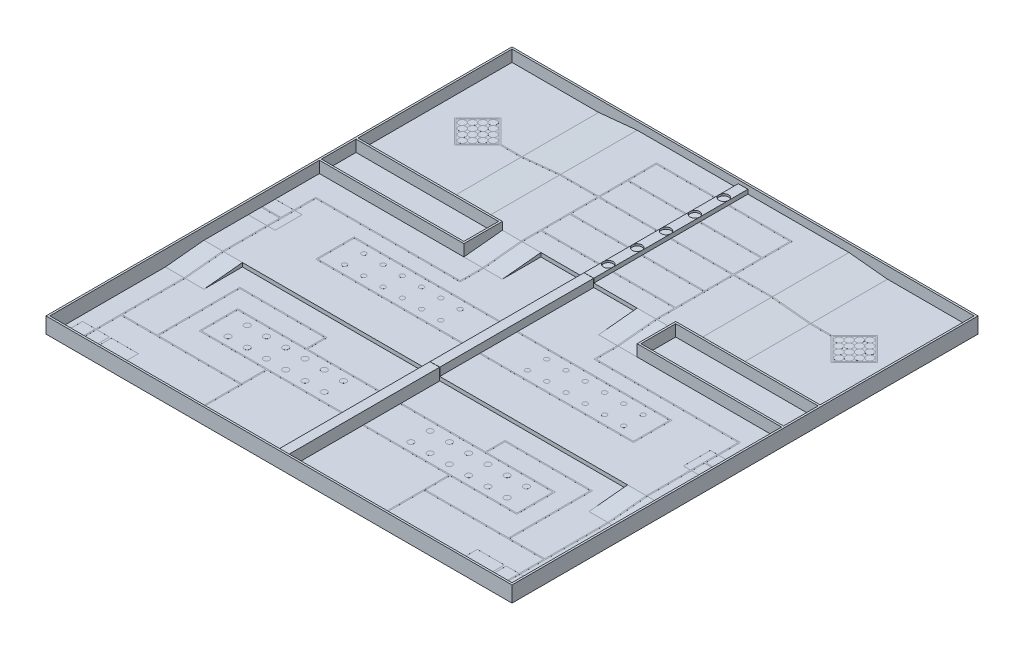
SolidWorks part; units mm, degrees
ref_plane "Front Plane" through (0, 0, 0) normal (0, 0, 1) x (1, 0, 0)
ref_plane "Top Plane" through (0, 0, 0) normal (0, 1, 0) x (1, 0, 0)
ref_plane "Right Plane" through (0, 0, 0) normal (1, 0, 0) x (0, 0, -1)
sketch "Sketch1" plane through (0, 0, 0) normal (0, 1, 0) x (1, 0, 0)
  line L1 (-6050, 6050) -> (6050, 6050)
  line L2 (-6050, 6050) -> (-6050, -6050)
  line L3 (-6050, -6050) -> (6050, -6050)
  line L4 (6050, 6050) -> (6050, -6050)
  line L5 (-6050, 6050) -> (6050, -6050) construction
  line L6 (-6050, -6050) -> (6050, 6050) construction
  point P0 (0, 0)
  dimension "D1" = 12100
  dimension "D2" = 12100
extrude "Boss-Extrude1" add sketch "Sketch1" along normal blind 10
sketch "Sketch2" plane through (0, 10, 0) normal (0, 1, 0) x (1, 0, 0)
  line L0 (0, 6332.5328) -> (0, -6669.5431) construction
  line L1 (-125, 6050) -> (-125, -6050)
  line L2 (125, 6050) -> (125, -6050)
  line L3 (-125, 6050) -> (125, 6050)
  line L4 (6050, 6050) -> (-6050, 6050) construction
  line L5 (-125, -6050) -> (125, -6050)
  line L6 (-125, 6332.5328) -> (-125, -6669.5431) construction
  line L7 (125, 6332.5328) -> (125, -6669.5431) construction
  line L8 (-6050, -6050) -> (6050, -6050) construction
  dimension "D1" = 125
  dimension "D2" = 125
extrude "Boss-Extrude2" add sketch "Sketch2" along normal blind 310
sketch "Sketch3" plane through (0, 10, 0) normal (0, 1, 0) x (1, 0, 0)
  line L0 (-6000, -6000) -> (-6000, 6000)
  line L1 (-6050, -6050) -> (6050, -6050)
  line L2 (-6050, -6050) -> (-6050, 6050)
  line L3 (-6050, 6050) -> (6050, 6050)
  line L4 (6050, -6050) -> (6050, 6050)
  line L5 (-6050, -6050) -> (6050, 6050) construction
  line L6 (-6050, 6050) -> (6050, -6050) construction
  line L7 (-6000, 6000) -> (6000, 6000)
  line L8 (6000, -6000) -> (6000, 6000)
  line L9 (-6000, -6000) -> (6000, -6000)
  point P0 (0, 0)
  dimension "D1" = 50
extrude "Boss-Extrude3" add sketch "Sketch3" along normal blind 400
sketch "Sketch4" plane through (0, 10, 0) normal (0, 1, 0) x (1, 0, 0)
  line L0 (-6863.0858, 0) -> (7124.8929, 0) construction
  line L1 (-6050, -2000) -> (6050, -2000)
  line L2 (-6050, 2000) -> (6050, 2000)
  line L3 (-6050, 2000) -> (-6050, 0)
  line L4 (-6050, 6050) -> (-6050, -6050) construction
  line L5 (-6050, 0) -> (-6050, -2000)
  line L6 (6050, 2000) -> (6050, -2000)
  line L7 (6050, -6050) -> (6050, 6050) construction
  line L9 (-6863.0858, 2000) -> (7124.8929, 2000) construction
  line L10 (-6863.0858, -2000) -> (7124.8929, -2000) construction
  dimension "D1" = 2000
  dimension "D2" = 2000
extrude "Boss-Extrude4" add sketch "Sketch4" along normal blind 100
sketch "Sketch5" plane through (0, 10, 0) normal (0, 1, 0) x (1, 0, 0)
  line L0 (-6000, 6000) -> (-6000, 2000)
  line L1 (-6000, 2000) -> (6000, 2000)
  line L2 (6000, 2000) -> (6000, 6000)
  line L3 (6000, 6000) -> (-6000, 6000)
extrude "Boss-Extrude5" add sketch "Sketch5" along normal blind 200
sketch "Sketch8" plane through (0, 110, 0) normal (0, 1, 0) x (1, 0, 0)
  line L0 (2250, 2000) -> (2250, 1000)
  line L1 (6000, 2000) -> (125, 2000) construction
  line L2 (2250, 1000) -> (6050, 1000)
  line L3 (6050, -6050) -> (6050, 6050) construction
  line L4 (6050, 1000) -> (6050, 2000)
  line L5 (6050, 2000) -> (2250, 2000)
  line L6 (6000, 1950) -> (2300, 1950)
  line L7 (2300, 1950) -> (2300, 1050)
  line L8 (2300, 1050) -> (6000, 1050)
  line L9 (6000, 1050) -> (6000, 1950)
  line L10 (0, 6607.4153) -> (0, -6987.4348) construction
  line L11 (-6050, 1000) -> (-6050, 2000)
  line L12 (-2250, 1000) -> (-6050, 1000)
  line L13 (-2250, 2000) -> (-2250, 1000)
  line L14 (-6050, 2000) -> (-2250, 2000)
  line L15 (-6000, 1050) -> (-6000, 1950)
  line L16 (-2300, 1050) -> (-6000, 1050)
  line L17 (-2300, 1950) -> (-2300, 1050)
  line L18 (-6000, 1950) -> (-2300, 1950)
  dimension "D1" = 1000
  dimension "D2" = 3800
  dimension "D3" = 50
extrude "Boss-Extrude9" add sketch "Sketch8" along normal blind 300
sketch "Sketch9" plane through (0, 210, 0) normal (0, 1, 0) x (1, 0, 0)
  line L0 (6000, 6000) -> (2750, 6000)
  line L1 (6000, 6000) -> (125, 6000) construction
  line L2 (2750, 6000) -> (2750, 2000)
  line L3 (2750, 2000) -> (6000, 2000)
  line L4 (6000, 2000) -> (6000, 6000) construction
  line L5 (6000, 2000) -> (6000, 6000)
  line L6 (0, 7222.203) -> (0, -7135.0065) construction
  line L7 (-2750, 2000) -> (-6000, 2000)
  line L8 (-2750, 6000) -> (-2750, 2000)
  line L9 (-6000, 6000) -> (-2750, 6000)
  line L10 (-6000, 2000) -> (-6000, 6000)
  dimension "D1" = 3250
  dimension "D2" = 4000
extrude "Cut-Extrude2" cut sketch "Sketch9" against normal blind 100
sketch "Sketch10" plane through (0, 0, -6000) normal (0, 0, 1) x (1, 0, 0)
  line L0 (2750, 210) -> (2750, 110)
  line L1 (2750, 110) -> (3750, 110)
  line L2 (6000, 110) -> (2750, 110) construction
  line L3 (3750, 110) -> (2750, 210)
  line L4 (0, 741.9991) -> (0, -415.2884) construction
  line L5 (-2750, 110) -> (-3750, 110)
  line L6 (-2750, 210) -> (-2750, 110)
  line L7 (-3750, 110) -> (-2750, 210)
  dimension "D1" = 1000
extrude "Boss-Extrude10" add sketch "Sketch10" along normal blind 4000
sketch "Sketch11" plane through (2250, 0, 0) normal (-1, 0, 0) x (0, 0, 1)
  line L0 (-2000, 210) -> (-2000, 110)
  line L1 (-2000, 110) -> (-1000, 110)
  line L2 (-1000, 110) -> (-2000, 210)
extrude "Boss-Extrude11" add sketch "Sketch11" along normal blind 1000
sketch "Sketch12" plane through (-2250, 0, 0) normal (1, 0, 0) x (0, 0, -1)
  line L1 (2000, 210) -> (2000, 110)
  line L2 (2000, 110) -> (1000, 110)
  line L3 (1000, 110) -> (2000, 210)
extrude "Boss-Extrude12" add sketch "Sketch12" along normal blind 1000
sketch "Sketch13" plane through (6000, 0, 0) normal (-1, 0, 0) x (0, 0, 1)
  line L0 (2000, 110) -> (2000, 10)
  line L1 (2000, 10) -> (3000, 10)
  line L2 (6000, 10) -> (2000, 10) construction
  line L3 (3000, 10) -> (2000, 110)
  dimension "D1" = 1000
extrude "Boss-Extrude13" add sketch "Sketch13" along normal blind 1000
sketch "Sketch14" plane through (-6000, 0, 0) normal (1, 0, 0) x (0, 0, -1)
  line L0 (-2000, 110) -> (-2000, 10)
  line L1 (-2000, 10) -> (-3000, 10)
  line L2 (-3000, 10) -> (-2000, 110)
  dimension "D1" = 1000
extrude "Boss-Extrude14" add sketch "Sketch14" along normal blind 1000
sketch "Sketch15" plane through (0, 320, 0) normal (0, 1, 0) x (1, 0, 0)
  line L0 (-125, 2000) -> (125, 2000)
  line L1 (125, 2000) -> (125, 1995)
  line L2 (125, -6000) -> (125, 6000) construction
  line L3 (125, 1995) -> (-125, 1995)
  line L4 (-125, 2000) -> (-125, -2000) construction
  line L5 (-125, 1995) -> (-125, 2000)
  line L6 (-125, -2000) -> (125, -2000)
  line L7 (125, -2000) -> (125, -2005)
  line L8 (125, -6000) -> (125, -2000) construction
  line L9 (125, -2005) -> (-125, -2005)
  line L10 (-125, 6000) -> (-125, -6000) construction
  line L11 (-125, -2005) -> (-125, -2000)
  dimension "D1" = 5
  dimension "D2" = 5
extrude "Cut-Extrude3" cut sketch "Sketch15" against normal blind 300
sketch "Sketch16" plane through (0, 10, 0) normal (0, 1, 0) x (1, 0, 0)
  line L0 (0, 6376.018) -> (0, -6397.7606) construction
  line L1 (5850, -6000) -> (5850, -5300)
  line L2 (-6000, -6000) -> (6000, -6000) construction
  line L3 (5850, -5300) -> (5150, -5300)
  line L4 (5150, -5300) -> (5150, -6000)
  line L5 (125, -6000) -> (6000, -6000) construction
  line L6 (5150, -6000) -> (5850, -6000)
  line L7 (5100, -6000) -> (5100, -5300)
  line L8 (5100, -5300) -> (4400, -5300)
  line L9 (4400, -5300) -> (4400, -6000)
  line L10 (4400, -6000) -> (5100, -6000)
  line L11 (6000, -6000) -> (6000, -3000) construction
  line L12 (-4400, -5300) -> (-4400, -6000)
  line L13 (-5100, -5300) -> (-4400, -5300)
  line L14 (-5100, -6000) -> (-5100, -5300)
  line L15 (-4400, -6000) -> (-5100, -6000)
  line L16 (-5150, -5300) -> (-5150, -6000)
  line L17 (-5850, -5300) -> (-5150, -5300)
  line L18 (-5850, -6000) -> (-5850, -5300)
  line L19 (-5150, -6000) -> (-5850, -6000)
  dimension "D1" = 150
  dimension "D2" = 700
  dimension "D3" = 700
  dimension "D4" = 50
  dimension "D5" = 700
  dimension "D6" = 700
extrude "Cut-Extrude4" cut sketch "Sketch16" against normal blind 0.5
sketch "Sketch18" plane through (0, 110, 0) normal (0, 1, 0) x (1, 0, 0)
  line L0 (0, 6289.0476) -> (0, -6452.1171) construction
  line L1 (6000, -150) -> (5300, -150)
  line L2 (6000, -2000) -> (6000, 1000) construction
  line L3 (5300, -150) -> (5300, -850)
  line L4 (5300, -850) -> (6000, -850)
  line L5 (6000, -850) -> (6000, -150)
  line L6 (2250, 1000) -> (6000, 1000) construction
  line L7 (-5300, -850) -> (-6000, -850)
  line L8 (-5300, -150) -> (-5300, -850)
  line L9 (-6000, -150) -> (-5300, -150)
  line L10 (-6000, -850) -> (-6000, -150)
  dimension "D1" = 700
  dimension "D2" = 700
  dimension "D3" = 1150
extrude "Cut-Extrude5" cut sketch "Sketch18" against normal blind 0.5
sketch "Sketch19" plane through (0, 10, 0) normal (0, 1, 0) x (1, 0, 0)
  line L0 (0, 6386.8893) -> (0, -6636.9292) construction
  line L1 (4000, -6000) -> (4000, -5750)
  line L2 (125, -6000) -> (4400, -6000) construction
  line L3 (4000, -5750) -> (750, -5750)
  line L4 (750, -5750) -> (750, -6000)
  line L5 (750, -6000) -> (4000, -6000)
  line L6 (4400, -5300) -> (4400, -6000) construction
  line L7 (750, -5875) -> (4000, -5875) construction
  line L8 (-750, -6000) -> (-4000, -6000)
  line L9 (-750, -5750) -> (-750, -6000)
  line L10 (-4000, -5750) -> (-750, -5750)
  line L11 (-4000, -6000) -> (-4000, -5750)
  circle A0 centre (1000, -5875) radius 45
  circle A1 centre (1250, -5875) radius 45
  circle A2 centre (1500, -5875) radius 45
  circle A3 centre (1750, -5875) radius 45
  circle A4 centre (2000, -5875) radius 45
  circle A5 centre (2250, -5875) radius 45
  circle A6 centre (2500, -5875) radius 45
  circle A7 centre (2750, -5875) radius 45
  circle A8 centre (3000, -5875) radius 45
  circle A9 centre (3250, -5875) radius 45
  circle A10 centre (3500, -5875) radius 45
  circle A11 centre (3750, -5875) radius 45
  circle A12 centre (-3750, -5875) radius 45
  circle A13 centre (-3500, -5875) radius 45
  circle A14 centre (-3250, -5875) radius 45
  circle A15 centre (-3000, -5875) radius 45
  circle A16 centre (-2750, -5875) radius 45
  circle A17 centre (-2500, -5875) radius 45
  circle A18 centre (-2250, -5875) radius 45
  circle A19 centre (-2000, -5875) radius 45
  circle A20 centre (-1750, -5875) radius 45
  circle A21 centre (-1500, -5875) radius 45
  circle A22 centre (-1250, -5875) radius 45
  circle A23 centre (-1000, -5875) radius 45
  dimension "D4" = 90
  dimension "D1" = 400
  dimension "D2" = 3250
  dimension "D3" = 250
  dimension "D5" = 250
  dimension "D7" = 2750
  dimension "D6" = 12
extrude "Boss-Extrude15" add sketch "Sketch19" along normal blind 60
sketch "Sketch20" plane through (0, 10, 0) normal (0, 1, 0) x (1, 0, 0)
  line L0 (0, 6278.1763) -> (0, -6517.3449) construction
  line L1 (125, -6000) -> (125, -2000) construction
  line L2 (125, -6000) -> (750, -6000) construction
  line L3 (125, -6000) -> (125, -2005) construction
  circle A0 centre (1125, -3750) radius 75
  circle A1 centre (1625, -3750) radius 75
  circle A2 centre (2125, -3750) radius 75
  circle A3 centre (2625, -3750) radius 75
  circle A4 centre (3125, -3750) radius 75
  circle A5 centre (3625, -3750) radius 75
  circle A6 centre (1625, -3250) radius 75
  circle A7 centre (2125, -3250) radius 75
  circle A8 centre (2625, -3250) radius 75
  circle A9 centre (3125, -3250) radius 75
  circle A10 centre (3625, -3250) radius 75
  circle A11 centre (1125, -3250) radius 75
  circle A12 centre (-1125, -3250) radius 75
  circle A13 centre (-3625, -3250) radius 75
  circle A14 centre (-3125, -3250) radius 75
  circle A15 centre (-2625, -3250) radius 75
  circle A16 centre (-2125, -3250) radius 75
  circle A17 centre (-1625, -3250) radius 75
  circle A18 centre (-3625, -3750) radius 75
  circle A19 centre (-3125, -3750) radius 75
  circle A20 centre (-2625, -3750) radius 75
  circle A21 centre (-2125, -3750) radius 75
  circle A22 centre (-1625, -3750) radius 75
  circle A23 centre (-1125, -3750) radius 75
  dimension "D1" = 150
  dimension "D2" = 2250
  dimension "D3" = 1000
  dimension "D6" = 500
  dimension "D7" = 2500
  dimension "D8" = 1000
  dimension "D4" = 6
  dimension "D5" = 2
extrude "Boss-Extrude16" add sketch "Sketch20" along normal blind 0.5
sketch "Sketch21" plane through (0, 9.5, 0) normal (0, 1, 0) x (1, 0, 0)
  line L0 (5500, -6000) -> (5500, -3000) construction
  line L1 (5150, -6000) -> (5850, -6000) construction
  line L2 (5000, -3000) -> (6000, -3000) construction
  line L3 (5485, -5300) -> (5485, -5635)
  line L4 (5850, -5300) -> (5150, -5300) construction
  line L5 (5150, -5650) -> (5850, -5650) construction
  line L6 (5150, -5300) -> (5150, -6000) construction
  line L7 (5850, -6000) -> (5850, -5300) construction
  line L8 (5515, -5300) -> (5515, -5635)
  line L9 (5150, -5665) -> (5485, -5665)
  line L10 (5150, -5635) -> (5485, -5635)
  line L12 (5850, -5635) -> (5850, -5665)
  line L13 (5485, -6000) -> (5515, -6000)
  line L14 (5150, -5635) -> (5150, -5665)
  line L15 (5485, -5665) -> (5485, -6000)
  line L16 (5515, -5635) -> (5850, -5635)
  line L17 (5515, -5665) -> (5515, -6000)
  line L18 (5150, -5635) -> (5850, -5635) construction
  line L19 (5515, -5665) -> (5850, -5665)
  line L20 (5485, -5300) -> (5485, -3000)
  line L21 (5150, -5665) -> (5850, -5665) construction
  line L22 (5515, -5300) -> (5515, -3000)
  line L23 (5485, -3000) -> (5515, -3000)
  line L24 (0, 6769.1351) -> (0, -7021.8172) construction
  line L25 (-5150, -5650) -> (-5850, -5650) construction
  line L26 (-5500, -6000) -> (-5500, -3000) construction
  line L27 (-5485, -3000) -> (-5515, -3000)
  line L28 (-5515, -5300) -> (-5515, -3000)
  line L29 (-5485, -5300) -> (-5485, -3000)
  line L30 (-5515, -5665) -> (-5850, -5665)
  line L31 (-5515, -5665) -> (-5515, -6000)
  line L32 (-5515, -5635) -> (-5850, -5635)
  line L33 (-5485, -5665) -> (-5485, -6000)
  line L34 (-5150, -5635) -> (-5150, -5665)
  line L35 (-5485, -6000) -> (-5515, -6000)
  line L36 (-5850, -5635) -> (-5850, -5665)
  line L37 (-5150, -5635) -> (-5485, -5635)
  line L38 (-5150, -5665) -> (-5485, -5665)
  line L39 (-5515, -5300) -> (-5515, -5635)
  line L40 (-5485, -5300) -> (-5485, -5635)
  dimension "D1" = 15
  dimension "D2" = 15
  dimension "D3" = 15
extrude "Boss-Extrude17" add sketch "Sketch21" along normal blind 1
sketch "Sketch22" plane through (0, 10, 0) normal (0, 1, 0) x (1, 0, 0)
  line L0 (5485, -4650) -> (2390, -4650) construction
  line L1 (5485, -5300) -> (5485, -3000) construction
  line L2 (-125, -3970) -> (-125, -4000)
  line L3 (5100, -5300) -> (4400, -5300) construction
  line L4 (4400, -5300) -> (4400, -6000) construction
  line L5 (-4548, -4635) -> (-2390, -4635)
  line L6 (5485, -4635) -> (4578, -4635)
  line L7 (5485, -4665) -> (2390, -4665)
  line L8 (5485, -4635) -> (5485, -4665)
  line L9 (2390, -5750) -> (2390, -4665)
  line L10 (4000, -5750) -> (750, -5750) construction
  line L11 (2360, -5750) -> (2360, -4000)
  line L12 (4000, -5750) -> (750, -5750) construction
  line L13 (2360, -4000) -> (125, -4000)
  line L14 (-2360, -5750) -> (-2390, -5750)
  line L15 (-4095, -3030) -> (-4095, -3970)
  line L17 (125, -6000) -> (125, -2005) construction
  line L18 (125, -3970) -> (4095, -3970)
  line L19 (4125, -3000) -> (4125, -4000)
  line L20 (4125, -3000) -> (2340, -3000)
  line L21 (2340, -3000) -> (2340, -2520)
  line L22 (2340, -2520) -> (4548, -2520)
  line L23 (4548, -2520) -> (4548, -4635)
  line L24 (4578, -4635) -> (4578, -2490)
  line L25 (4578, -2490) -> (2310, -2490)
  line L26 (2310, -2490) -> (2310, -3000)
  line L27 (2310, -3000) -> (125, -3000)
  line L28 (125, -6000) -> (125, -2000) construction
  line L29 (125, -3000) -> (125, -3030)
  line L30 (4125, -4000) -> (2390, -4000)
  line L31 (2390, -4000) -> (2390, -4635)
  line L32 (125, -3030) -> (4095, -3030)
  line L33 (4095, -3030) -> (4095, -3970)
  line L34 (125, -6000) -> (750, -6000) construction
  line L35 (2360, -5750) -> (2390, -5750)
  line L36 (4548, -4635) -> (2390, -4635)
  line L37 (125, -3970) -> (125, -4000)
  line L38 (5485, -4635) -> (2390, -4635) construction
  line L39 (0, 6467.6788) -> (0, -7119.9213) construction
  line L40 (-125, -3030) -> (-4095, -3030)
  line L41 (-2390, -4000) -> (-2390, -4635)
  line L42 (-4125, -4000) -> (-2390, -4000)
  line L43 (-125, -3000) -> (-125, -3030)
  line L44 (-2310, -3000) -> (-125, -3000)
  line L45 (-2310, -2490) -> (-2310, -3000)
  line L46 (-4578, -2490) -> (-2310, -2490)
  line L47 (-4578, -4635) -> (-4578, -2490)
  line L48 (-4548, -2520) -> (-4548, -4635)
  line L49 (-2340, -2520) -> (-4548, -2520)
  line L50 (-2340, -3000) -> (-2340, -2520)
  line L51 (-4125, -3000) -> (-2340, -3000)
  line L52 (-4125, -3000) -> (-4125, -4000)
  line L53 (-125, -3970) -> (-4095, -3970)
  line L54 (-2360, -4000) -> (-125, -4000)
  line L55 (-2360, -5750) -> (-2360, -4000)
  line L56 (-2390, -5750) -> (-2390, -4665)
  line L57 (-5485, -4635) -> (-5485, -4665)
  line L58 (-5485, -4665) -> (-2390, -4665)
  line L59 (-5485, -4635) -> (-4578, -4635)
  dimension "D8" = 4000
  dimension "D1" = 650
  dimension "D2" = 2010
  dimension "D5" = 30
  dimension "D6" = 1750
  dimension "D7" = 1000
  dimension "D9" = 30
  dimension "D10" = 30
  dimension "D11" = 30
  dimension "D12" = 30
  dimension "D13" = 30
  dimension "D14" = 480
  dimension "D15" = 30
  dimension "D16" = 2185
  dimension "D17" = 30
  dimension "D18" = 423
  dimension "D3" = 15
  dimension "D4" = 15
extrude "Boss-Extrude18" add sketch "Sketch22" along normal blind 0.5
ref_plane "Plane1" through (5515, 0, 0) normal (-1, 0, 0) x (0, 0, 1)
sketch "Sketch23" plane through (5515, 0, 0) normal (-1, 0, 0) x (0, 0, 1)
  line L0 (2000, 110) -> (2000, 110.5)
  line L1 (2000, 110.5) -> (3000, 10.5)
  line L2 (3000, 10.5) -> (3000, 10)
  line L3 (3000, 10) -> (2000, 110)
  line L4 (3000, 10) -> (2000, 110) construction
  line L7 (3000, 10.5) -> (3000, 10) construction
  dimension "D1" = 0.5
extrude "Boss-Extrude19" add sketch "Sketch23" along normal blind 30
ref_plane "Plane2" through (-5515, 0, 0) normal (1, 0, 0) x (0, 0, -1)
sketch "Sketch24" plane through (-5515, 0, 0) normal (1, 0, 0) x (0, 0, -1)
  line L1 (-3000, 10) -> (-3000, 10.5)
  line L2 (-3000, 10.5) -> (-2000, 110.5)
  line L3 (-2000, 110.5) -> (-2000, 110)
  line L4 (-2000, 110) -> (-3000, 10)
  line L5 (-2000, 110) -> (-3000, 10) construction
  line L7 (-3000, 10.5) -> (-3000, 10) construction
  dimension "D1" = 0.5
extrude "Boss-Extrude20" add sketch "Sketch24" along normal blind 30
sketch "Sketch25" plane through (0, 110, 0) normal (0, 1, 0) x (1, 0, 0)
  line L0 (5515, -2000) -> (5515, -515)
  line L1 (5515, -515) -> (6000, -515)
  line L2 (6000, -850) -> (6000, -150) construction
  line L3 (6000, -515) -> (6000, -485)
  line L4 (6000, -6000) -> (6000, 1000) construction
  line L5 (6000, -485) -> (5515, -485)
  line L6 (5515, -485) -> (5515, 420)
  line L7 (5515, 420) -> (1765, 420)
  line L8 (1765, 420) -> (1765, 1000)
  line L9 (1250, 1000) -> (2250, 1000) construction
  line L10 (1765, 1000) -> (1735, 1000)
  line L11 (1735, 1000) -> (1735, 390)
  line L12 (1735, 390) -> (5485, 390)
  line L13 (5485, 390) -> (5485, -2000)
  line L14 (5000, -2000) -> (5485, -2000) construction
  line L15 (5485, -2000) -> (5515, -2000)
  line L16 (5300, -850) -> (6000, -850) construction
  line L17 (2250, 1000) -> (2250, 2000) construction
  line L18 (2250, 1000) -> (6000, 1000) construction
  line L19 (0, 6919.2774) -> (0, -6916.6346) construction
  line L20 (-5485, -2000) -> (-5515, -2000)
  line L21 (-5485, 390) -> (-5485, -2000)
  line L22 (-1735, 390) -> (-5485, 390)
  line L23 (-1735, 1000) -> (-1735, 390)
  line L24 (-1765, 1000) -> (-1735, 1000)
  line L25 (-1765, 420) -> (-1765, 1000)
  line L26 (-5515, 420) -> (-1765, 420)
  line L27 (-5515, -485) -> (-5515, 420)
  line L28 (-6000, -485) -> (-5515, -485)
  line L29 (-6000, -515) -> (-6000, -485)
  line L30 (-5515, -515) -> (-6000, -515)
  line L31 (-5515, -2000) -> (-5515, -515)
  dimension "D1" = 30
  dimension "D2" = 30
  dimension "D3" = 30
  dimension "D4" = 335
  dimension "D5" = 30
  dimension "D6" = 30
  dimension "D7" = 485
  dimension "D8" = 580
extrude "Boss-Extrude21" add sketch "Sketch25" along normal blind 0.5
sketch "Sketch26" plane through (0, 110, 0) normal (0, 1, 0) x (1, 0, 0)
  line L0 (125, 27.5) -> (4125, 27.5)
  line L1 (125, -2000) -> (125, 1995) construction
  line L2 (4125, 27.5) -> (4125, -972.5)
  line L3 (4125, -972.5) -> (125, -972.5)
  line L4 (125, -942.5) -> (4095, -942.5)
  line L5 (125, -2000) -> (125, 1995) construction
  line L6 (4095, -942.5) -> (4095, -2.5)
  line L7 (4095, -2.5) -> (125, -2.5)
  line L8 (125, -2.5) -> (125, 27.5)
  line L9 (0, 6616.8381) -> (0, -6826.6708) construction
  line L10 (-125, -2.5) -> (-125, 27.5)
  line L11 (-4095, -2.5) -> (-125, -2.5)
  line L12 (-4095, -942.5) -> (-4095, -2.5)
  line L13 (-125, -942.5) -> (-4095, -942.5)
  line L14 (-4125, -972.5) -> (-125, -972.5)
  line L15 (-4125, 27.5) -> (-4125, -972.5)
  line L16 (-125, 27.5) -> (-4125, 27.5)
  line L17 (-125, -942.5) -> (-125, -972.5)
  line L18 (125, -942.5) -> (125, -972.5)
  circle A0 centre (3625, -222.5) radius 60
  circle A1 centre (3125, -222.5) radius 60
  circle A2 centre (2625, -222.5) radius 60
  circle A3 centre (2125, -222.5) radius 60
  circle A4 centre (1625, -222.5) radius 60
  circle A5 centre (1125, -222.5) radius 60
  circle A6 centre (3125, -722.5) radius 60
  circle A7 centre (2625, -722.5) radius 60
  circle A8 centre (2125, -722.5) radius 60
  circle A9 centre (1625, -722.5) radius 60
  circle A10 centre (1125, -722.5) radius 60
  circle A11 centre (3625, -722.5) radius 60
  circle A12 centre (-3625, -722.5) radius 60
  circle A13 centre (-1125, -722.5) radius 60
  circle A14 centre (-1625, -722.5) radius 60
  circle A15 centre (-2125, -722.5) radius 60
  circle A16 centre (-2625, -722.5) radius 60
  circle A17 centre (-3125, -722.5) radius 60
  circle A18 centre (-1125, -222.5) radius 60
  circle A19 centre (-1625, -222.5) radius 60
  circle A20 centre (-2125, -222.5) radius 60
  circle A21 centre (-2625, -222.5) radius 60
  circle A22 centre (-3125, -222.5) radius 60
  circle A23 centre (-3625, -222.5) radius 60
  dimension "D6" = 120
  dimension "D1" = 30
  dimension "D2" = 30
  dimension "D3" = 30
  dimension "D4" = 1000
  dimension "D5" = 4000
  dimension "D7" = 250
  dimension "D8" = 500
  dimension "D11" = 2500
  dimension "D12" = 500
  dimension "D13" = 500
  dimension "D9" = 6
  dimension "D10" = 2
extrude "Boss-Extrude22" add sketch "Sketch26" along normal blind 0.5
ref_plane "Plane3" through (1765, 0, 0) normal (-1, 0, 0) x (0, 0, 1)
sketch "Sketch27" plane through (1765, 0, 0) normal (-1, 0, 0) x (0, 0, 1)
  line L1 (-2000, 210) -> (-1000, 110)
  line L2 (-1000, 110) -> (-1000, 110.5)
  line L3 (-1000, 110.5) -> (-2000, 210.5)
  line L4 (-2000, 210.5) -> (-2000, 210)
  line L5 (-1000, 110) -> (-2000, 210) construction
  line L7 (-1000, 110.5) -> (-1000, 110) construction
  dimension "D1" = 0.5
extrude "Boss-Extrude23" add sketch "Sketch27" along normal blind 30
ref_plane "Plane4" through (-1765, 0, 0) normal (1, 0, 0) x (0, 0, -1)
sketch "Sketch28" plane through (-1765, 0, 0) normal (1, 0, 0) x (0, 0, -1)
  line L1 (1000, 110) -> (2000, 210)
  line L2 (2000, 210) -> (2000, 210.5)
  line L3 (2000, 210.5) -> (1000, 110.5)
  line L4 (1000, 110.5) -> (1000, 110)
  line L5 (2000, 210) -> (1000, 110) construction
  line L6 (1000, 110.5) -> (1000, 110) construction
  dimension "D1" = 0.5
extrude "Boss-Extrude24" add sketch "Sketch28" along normal blind 30
sketch "Sketch29" plane through (0, 210, 0) normal (0, 1, 0) x (1, 0, 0)
  line L0 (1765, 2000) -> (1765, 3985)
  line L1 (1765, 3985) -> (2750, 3985)
  line L3 (2750, 6000) -> (2750, 2000) construction
  line L4 (2750, 3985) -> (2750, 4015)
  line L5 (2750, 4015) -> (1765, 4015)
  line L6 (1765, 4015) -> (1765, 5515)
  line L7 (1765, 5515) -> (125, 5515)
  line L8 (125, 2000) -> (125, 6000) construction
  line L9 (125, 5515) -> (125, 5485)
  line L10 (125, 5485) -> (1735, 5485)
  line L11 (1735, 5485) -> (1735, 4765)
  line L12 (1735, 4765) -> (125, 4765)
  line L13 (125, 2000) -> (125, 6000) construction
  line L14 (125, 4765) -> (125, 4735)
  line L15 (125, 4735) -> (1735, 4735)
  line L16 (1735, 4735) -> (1735, 4015)
  line L17 (1735, 4015) -> (125, 4015)
  line L18 (125, 4015) -> (125, 3985)
  line L19 (125, 3985) -> (1735, 3985)
  line L20 (1735, 3985) -> (1735, 3265)
  line L21 (1735, 3265) -> (125, 3265)
  line L22 (125, 3265) -> (125, 3235)
  line L23 (125, 3235) -> (1735, 3235)
  line L24 (1735, 3235) -> (1735, 2515)
  line L25 (1735, 2515) -> (125, 2515)
  line L26 (125, 2515) -> (125, 2485)
  line L27 (125, 2485) -> (1735, 2485)
  line L28 (1735, 2485) -> (1735, 2000)
  line L29 (1735, 2000) -> (1765, 2000)
  line L30 (2750, 6000) -> (125, 6000) construction
  line L31 (1765, 2000) -> (2250, 2000) construction
  line L32 (0, 6376.8672) -> (0, -1004.6373) construction
  line L33 (-1735, 2000) -> (-1765, 2000)
  line L34 (-1735, 2485) -> (-1735, 2000)
  line L35 (-125, 2485) -> (-1735, 2485)
  line L36 (-125, 2515) -> (-125, 2485)
  line L37 (-1735, 2515) -> (-125, 2515)
  line L38 (-1735, 3235) -> (-1735, 2515)
  line L39 (-125, 3235) -> (-1735, 3235)
  line L40 (-125, 3265) -> (-125, 3235)
  line L41 (-1735, 3265) -> (-125, 3265)
  line L42 (-1735, 3985) -> (-1735, 3265)
  line L43 (-125, 3985) -> (-1735, 3985)
  line L44 (-125, 4015) -> (-125, 3985)
  line L45 (-1735, 4015) -> (-125, 4015)
  line L46 (-1735, 4735) -> (-1735, 4015)
  line L47 (-125, 4735) -> (-1735, 4735)
  line L48 (-125, 4765) -> (-125, 4735)
  line L49 (-1735, 4765) -> (-125, 4765)
  line L50 (-1735, 5485) -> (-1735, 4765)
  line L51 (-125, 5485) -> (-1735, 5485)
  line L52 (-125, 5515) -> (-125, 5485)
  line L53 (-1765, 5515) -> (-125, 5515)
  line L54 (-1765, 4015) -> (-1765, 5515)
  line L55 (-2750, 4015) -> (-1765, 4015)
  line L56 (-2750, 3985) -> (-2750, 4015)
  line L57 (-1765, 3985) -> (-2750, 3985)
  line L58 (-1765, 2000) -> (-1765, 3985)
  dimension "D1" = 30
  dimension "D2" = 30
  dimension "D3" = 30
  dimension "D4" = 30
  dimension "D5" = 1985
  dimension "D6" = 1985
  dimension "D7" = 30
  dimension "D8" = 485
  dimension "D9" = 30
  dimension "D10" = 30
  dimension "D11" = 720
  dimension "D12" = 30
  dimension "D13" = 30
  dimension "D14" = 720
  dimension "D15" = 720
extrude "Boss-Extrude25" add sketch "Sketch29" along normal blind 0.5
ref_plane "Plane5" through (0, 0, -4015) normal (0, 0, 1) x (1, 0, 0)
sketch "Sketch30" plane through (0, 0, -4015) normal (0, 0, 1) x (1, 0, 0)
  line L1 (2750, 210) -> (3750, 110)
  line L2 (3750, 110) -> (3750, 110.5)
  line L3 (3750, 110.5) -> (2750, 210.5)
  line L4 (2750, 210.5) -> (2750, 210)
  line L5 (-2750, 210) -> (-3750, 110)
  line L6 (-3750, 110) -> (-3750, 110.5)
  line L7 (-3750, 110.5) -> (-2750, 210.5)
  line L8 (-2750, 210.5) -> (-2750, 210)
  line L9 (3750, 110) -> (2750, 210) construction
  line L10 (2750, 210.5) -> (2750, 210) construction
  line L11 (-2750, 210) -> (-3750, 110) construction
  line L12 (-2750, 210.5) -> (-2750, 210) construction
  dimension "D1" = 0.5
  dimension "D2" = 0.5
extrude "Boss-Extrude26" add sketch "Sketch30" along normal blind 30
sketch "Sketch31" plane through (0, 110, 0) normal (0, 1, 0) x (1, 0, 0)
  line L0 (3750, 4000) -> (5893.5836, 4000) construction
  line L1 (3750, 3985) -> (3750, 4015) construction
  line L2 (4890.0408, 4992.3625) -> (4890.0408, 3149.0483) construction
  line L3 (0, 6735.0907) -> (0, -332.6816) construction
  line L4 (4890.0408, 4601.0408) -> (4304, 4015)
  line L9 (4304, 3985) -> (4890.0408, 3398.9592)
  line L10 (4890.0408, 3398.9592) -> (5491.0815, 4000)
  line L11 (5491.0815, 4000) -> (4890.0408, 4601.0408)
  line L12 (-4890.0408, 4992.3625) -> (-4890.0408, 3149.0483) construction
  line L13 (3750, 4015) -> (4304, 4015)
  line L14 (3750, 4015) -> (3750, 3985)
  line L15 (3750, 3985) -> (4304, 3985)
  line L16 (5448.6551, 4000) -> (4890.0408, 4558.6144)
  line L17 (4890.0408, 4558.6144) -> (4331.4264, 4000)
  line L18 (4331.4264, 4000) -> (4890.0408, 3441.3856)
  line L19 (4890.0408, 3441.3856) -> (5448.6551, 4000)
  line L20 (3750, 4015) -> (3750, 6000) construction
  line L21 (4890.0408, 4601.0408) -> (4289, 4000) construction
  line L22 (4289, 4000) -> (4890.0408, 3398.9592) construction
  line L23 (6000, 2000) -> (6000, 6000) construction
  line L24 (-3750, 4000) -> (-5893.5836, 4000) construction
  line L25 (-4890.0408, 3441.3856) -> (-5448.6551, 4000)
  line L26 (-4331.4264, 4000) -> (-4890.0408, 3441.3856)
  line L27 (-4890.0408, 4558.6144) -> (-4331.4264, 4000)
  line L28 (-5448.6551, 4000) -> (-4890.0408, 4558.6144)
  line L29 (-3750, 3985) -> (-4304, 3985)
  line L30 (-3750, 4015) -> (-3750, 3985)
  line L31 (-3750, 4015) -> (-4304, 4015)
  line L32 (-5491.0815, 4000) -> (-4890.0408, 4601.0408)
  line L33 (-4890.0408, 3398.9592) -> (-5491.0815, 4000)
  line L34 (-4304, 3985) -> (-4890.0408, 3398.9592)
  line L35 (-4890.0408, 4601.0408) -> (-4304, 4015)
  point P8 (4890.0408, 4000)
  point P40 (-4890.0408, 4000)
  dimension "D1" = 1140.0408
  dimension "D2" = 508.9185
  dimension "D3" = 850
  dimension "D4" = 30
extrude "Boss-Extrude27" add sketch "Sketch31" along normal blind 0.5
sketch "Sketch32" plane through (0, 110, 0) normal (0, 1, 0) x (1, 0, 0)
  line L0 (0, 6397.7606) -> (0, -549.0007) construction
  line L1 (5169.3479, 4279.3072) -> (4610.7336, 3720.6928) construction
  line L2 (5448.6551, 4000) -> (4890.0408, 4558.6144) construction
  line L3 (4610.7336, 4279.3072) -> (5169.3479, 3720.6928) construction
  line L4 (4890.0408, 4558.6144) -> (4331.4264, 4000) construction
  line L5 (4890.0408, 3441.3856) -> (5448.6551, 4000) construction
  line L6 (4331.4264, 4000) -> (4890.0408, 3441.3856) construction
  line L7 (4677.9087, 4346.4823) -> (5236.5231, 3787.868) construction
  line L8 (5102.1728, 4346.4823) -> (4543.5584, 3787.868) construction
  line L9 (5034.9977, 4413.6575) -> (4476.3833, 3855.0431) construction
  line L10 (4476.3833, 4144.9569) -> (5034.9977, 3586.3425) construction
  line L11 (4745.0839, 4413.6575) -> (5303.6982, 3855.0431) construction
  line L12 (-4745.0839, 4413.6575) -> (-5303.6982, 3855.0431) construction
  line L13 (-4476.3833, 4144.9569) -> (-5034.9977, 3586.3425) construction
  line L14 (-5034.9977, 4413.6575) -> (-4476.3833, 3855.0431) construction
  line L15 (-5102.1728, 4346.4823) -> (-4543.5584, 3787.868) construction
  line L16 (-4677.9087, 4346.4823) -> (-5236.5231, 3787.868) construction
  line L17 (-4610.7336, 4279.3072) -> (-5169.3479, 3720.6928) construction
  line L18 (-5169.3479, 4279.3072) -> (-4610.7336, 3720.6928) construction
  circle A1 centre (4890.0408, 4134.3503) radius 94.5
  circle A2 centre (4755.6905, 4268.7006) radius 94.5
  circle A3 centre (5024.3911, 4000) radius 94.5
  circle A4 centre (5158.7413, 3865.6497) radius 94.5
  circle A5 centre (5024.3911, 3731.2994) radius 94.5
  circle A6 centre (4890.0408, 3865.6497) radius 94.5
  circle A7 centre (4755.6905, 4000) radius 94.5
  circle A8 centre (4621.3402, 4134.3503) radius 94.5
  circle A9 centre (4890.0408, 3596.9491) radius 94.5
  circle A10 centre (4755.6905, 3731.2994) radius 94.5
  circle A11 centre (4621.3402, 3865.6497) radius 94.5
  circle A12 centre (4486.9899, 4000) radius 94.5
  circle A13 centre (5293.0916, 4000) radius 94.5
  circle A14 centre (5158.7413, 4134.3503) radius 94.5
  circle A15 centre (5024.3911, 4268.7006) radius 94.5
  circle A16 centre (4890.0408, 4403.0509) radius 94.5
  circle A17 centre (-4890.0408, 4403.0509) radius 94.5
  circle A18 centre (-5024.3911, 4268.7006) radius 94.5
  circle A19 centre (-5158.7413, 4134.3503) radius 94.5
  circle A20 centre (-5293.0916, 4000) radius 94.5
  circle A21 centre (-4486.9899, 4000) radius 94.5
  circle A22 centre (-4621.3402, 3865.6497) radius 94.5
  circle A23 centre (-4755.6905, 3731.2994) radius 94.5
  circle A24 centre (-4890.0408, 3596.9491) radius 94.5
  circle A25 centre (-4621.3402, 4134.3503) radius 94.5
  circle A26 centre (-4755.6905, 4000) radius 94.5
  circle A27 centre (-4890.0408, 3865.6497) radius 94.5
  circle A28 centre (-5024.3911, 3731.2994) radius 94.5
  circle A29 centre (-5158.7413, 3865.6497) radius 94.5
  circle A30 centre (-5024.3911, 4000) radius 94.5
  circle A31 centre (-4755.6905, 4268.7006) radius 94.5
  circle A32 centre (-4890.0408, 4134.3503) radius 94.5
  dimension "D3" = 189
  dimension "D1" = 95
  dimension "D2" = 95
  dimension "D4" = 95
  dimension "D5" = 190
  dimension "D6" = 190
extrude "Boss-Extrude30" add sketch "Sketch32" along normal blind 0.5
sketch "Sketch33" plane through (0, 320, 0) normal (0, 1, 0) x (1, 0, 0)
  line L1 (0, 6138.292) -> (0, -135.4617) construction
  line L2 (-125, 5500) -> (125, 5500) construction
  line L3 (-125, 5485) -> (-125, 5515) construction
  line L4 (125, 5515) -> (125, 5485) construction
  line L5 (-125, 4750) -> (125, 4750) construction
  line L6 (-125, 4735) -> (-125, 4765) construction
  line L7 (125, 4765) -> (125, 4735) construction
  line L8 (-125, 4000) -> (125, 4000) construction
  line L9 (-125, 3985) -> (-125, 4015) construction
  line L10 (125, 4015) -> (125, 3985) construction
  line L11 (-125, 3250) -> (125, 3250) construction
  line L12 (-125, 3235) -> (-125, 3265) construction
  line L13 (125, 2000) -> (125, 6000) construction
  line L14 (-125, 2500) -> (125, 2500) construction
  line L15 (-125, 2485) -> (-125, 2515) construction
  circle A0 centre (0, 5500) radius 124.5
  circle A1 centre (0, 4750) radius 124.5
  circle A2 centre (0, 4000) radius 124.5
  circle A3 centre (0, 3250) radius 124.5
  circle A4 centre (0, 2500) radius 124.5
  point P33 (0, 2500)
  dimension "D1" = 249
  dimension "D3" = 3000
  dimension "D2" = 5
extrude "Cut-Extrude6" cut sketch "Sketch33" against normal blind 50
